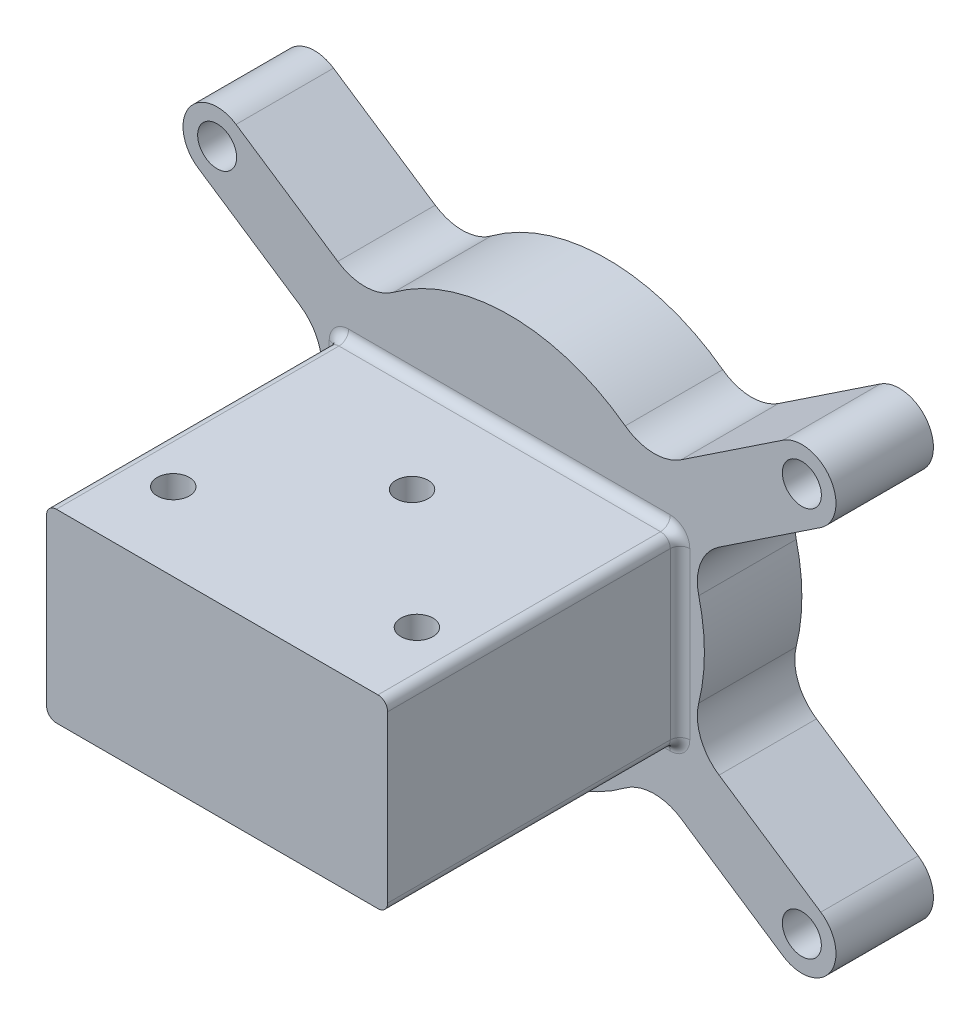
SolidWorks part; units mm, degrees
note: '?' marks a value the reader was unsure of. The reader was unsure of these and kept them because the rebuilt part matched: thickness of "Base-Flange1", "Sheet-Metal8", "Sheet-Metal9", "Sheet-Metal11", "Sheet-Metal12", "Sheet-Metal13".
material "3.3547 (EN-AW 5083)"
ref_plane "Front Plane" through (0, 0, 0) normal (0, 0, 1) x (1, 0, 0)
ref_plane "Top Plane" through (0, 0, 0) normal (0, 1, 0) x (1, 0, 0)
ref_plane "Right Plane" through (0, 0, 0) normal (1, 0, 0) x (0, 0, -1)
ref_axis "Axis1" through (0, 0, -55.9602) along (0, 0, 1)?
sketch "Sketch1" plane through (0, 0, 0) normal (0, 0, 1) x (1, 0, 0)
  line L0 (0, 0) -> (30, 20) construction
  line L2 (14.4428, 13.835) -> (28.0585, 22.9122)
  line L4 (18.3257, 8.0106) -> (31.9415, 17.0878)
  line L5 (0, -44.7868) -> (0, 44.7868) construction
  line L6 (14.4428, -13.835) -> (28.0585, -22.9122)
  line L7 (55, 0) -> (-55, 0) construction
  line L8 (18.3257, -8.0106) -> (31.9415, -17.0878)
  line L9 (-14.4428, -13.835) -> (-28.0585, -22.9122)
  line L10 (-14.4428, 13.835) -> (-28.0585, 22.9122)
  line L11 (-18.3257, 8.0106) -> (-31.9415, 17.0878)
  line L12 (-18.3257, -8.0106) -> (-31.9415, -17.0878)
  line L13 (0, 0) -> (30, -20) construction
  line L14 (0, 0) -> (-30, 20) construction
  line L15 (-30, 20) -> (0, 0) construction
  line L16 (0, 0) -> (-30, -20) construction
  arc A0 (31.9415, 17.0878) -> (28.0585, 22.9122) centre (30, 20) ccw
  arc A1 (28.0585, -22.9122) -> (31.9415, -17.0878) centre (30, -20) ccw
  arc A5 (-31.9415, 17.0878) -> (-28.0585, 22.9122) centre (-30, 20) cw
  arc A6 (-28.0585, -22.9122) -> (-31.9415, -17.0878) centre (-30, -20) cw
  arc A7 (-18.3257, 8.0106) -> (-18.3257, -8.0106) centre (0, 0) ccw
  arc A8 (-14.4428, -13.835) -> (14.4428, -13.835) centre (0, 0) ccw
  arc A9 (14.4428, 13.835) -> (-14.4428, 13.835) centre (0, 0) ccw
  arc A10 (18.3257, -8.0106) -> (18.3257, 8.0106) centre (0, 0) ccw
  point P2 (0, 0)
  dimension "D1" = 7
  dimension "D3" = 40
  dimension "D5" = 40
  dimension "D4" = 20
  dimension "D2" = 30
base flange "Base-Flange1" sketch "Sketch1" thickness 10 reverse thickness direction no parameters "D1"=1.6
sketch "Sketch8" plane through (0, 0, 0) normal (0, 0, 1) x (1, 0, 0)
  arc A0 (31.9415, 17.0878) -> (28.0585, 22.9122) centre (30, 20) ccw construction
  arc A1 (28.0585, -22.9122) -> (31.9415, -17.0878) centre (30, -20) ccw construction
  arc A2 (-31.9415, -17.0878) -> (-28.0585, -22.9122) centre (-30, -20) ccw construction
  arc A3 (-28.0585, 22.9122) -> (-31.9415, 17.0878) centre (-30, 20) ccw construction
  point P0 (-30, 20)
  point P2 (30, -20)
  point P4 (-30, -20)
  point P6 (-30, 20)
  point P11 (30, 20)
hole_wizard "Ø4.0mm Dowel Hole1" positions "Sketch8" profile "Sketch9" hole size "Ø4.0" standard "ISO"
sketch "Sketch9" plane through (-30, 20, 0) normal (1, 0, 0) x (0, -1, 0)
  line L0 (0, 0) -> (0, 17.2017)
  line L1 (0, 17.2017) -> (2, 16)
  line L2 (2, 16) -> (2, 0)
  line L5 (2, 0) -> (0, 0)
  line L10 (0, 17.2017) -> (-2, 16) construction
  line L11 (0, -6.35) -> (0, 107.95) construction
  dimension "Hole Dia." = 4
  dimension "Hole Depth" = 16
  dimension "Drill Angle" = 118
fillet "Fillet1" radius 5 8 edges at (-18.3257, 8.0106, -5) (-18.3257, -8.0106, -5) (-14.4428, -13.835, -5) (14.4428, -13.835, -5) (18.3257, -8.0106, -5) (18.3257, 8.0106, -5) (14.4428, 13.835, -5) (-14.4428, 13.835, -5)
sketch "Sketch10" plane through (0, 0, 0) normal (0, 0, 1) x (1, 0, 0)
  line L2 (-7, -7.1414) -> (-7, 7.1414)
  line L4 (7, -7.1414) -> (7, 7.1414)
  line L5 (-7, -7.1414) -> (7, 7.1414) construction
  line L6 (-7, 7.1414) -> (7, -7.1414) construction
  arc A0 (-7, -7.1414) -> (7, -7.1414) centre (0, 0) ccw
  arc A1 (7, 7.1414) -> (-7, 7.1414) centre (0, 0) ccw
  dimension "D1" = 20
  dimension "D2" = 14
sketch "Sketch15" plane through (0, 0, -10) normal (0, 0, -1) x (-1, 0, 0)
  point P0 (0, 0)
hole_wizard "Ø4.0mm Dowel Hole2" positions "Sketch15" profile "Sketch16" hole size "Ø4.0" standard "ISO"
sketch "Sketch16" plane through (0, 0, -10) normal (1, 0, 0) x (0, 1, 0)
  line L0 (0, 0) -> (0, 17.2017)
  line L1 (0, 17.2017) -> (2, 16)
  line L2 (2, 16) -> (2, 0)
  line L5 (2, 0) -> (0, 0)
  line L10 (0, 17.2017) -> (-2, 16) construction
  line L11 (0, -6.35) -> (0, 107.95) construction
  dimension "Hole Dia." = 4
  dimension "Hole Depth" = 16
  dimension "Drill Angle" = 118
sketch "Sketch17" plane through (0, 0, 0) normal (0, 0, 1) x (1, 0, 0)
  line L1 (-17.5, -9.5) -> (17.5, -9.5)
  line L2 (-17.5, -9.5) -> (-17.5, 9.5)
  line L3 (-17.5, 9.5) -> (17.5, 9.5)
  line L4 (17.5, -9.5) -> (17.5, 9.5)
  line L5 (-17.5, -9.5) -> (17.5, 9.5) construction
  line L6 (-17.5, 9.5) -> (17.5, -9.5) construction
  point P0 (0, 0)
  dimension "D1" = 19
  dimension "D2" = 35
extrude "Boss-Extrude1" add sketch "Sketch17" along normal blind 30
sketch "Sketch18" plane through (0, 9.5, 0) normal (0, 1, 0) x (1, 0, 0)
  line L0 (0, -44.7868) -> (0, 44.7868) construction
  line L1 (-17.5, -30) -> (-17.5, 0) construction
  line L2 (17.5, -30) -> (17.5, 0) construction
  line L3 (-44.2539, 0) -> (44.2539, 0) construction
  circle A0 centre (0, -10) radius 1.65
  circle A1 centre (-12.5, -22) radius 1.65
  circle A2 centre (12.5, -22) radius 1.65
  dimension "D1" = 3.3
  dimension "D2" = 5
  dimension "D3" = 5
  dimension "D4" = 10
  dimension "D5" = 22
extrude "Cut-Extrude1" cut sketch "Sketch18" against normal through all normal cut yes
fillet "Fillet2" radius 1 8 edges at (17.5, 0, 0) (0, 9.5, 0) (0, -9.5, 0) (-17.5, 0, 0) (-17.5, -9.5, 15) (17.5, -9.5, 15) (17.5, 9.5, 15) (-17.5, 9.5, 15)
sketch "Bend-Lines1" [suppressed] plane through (0, 0, 0) normal (0, 1, 0) x (1, 0, 0)
sketch "Bounding-Box1" [suppressed] plane through (0, 0, 0) normal (0, 1, 0) x (1, 0, 0)
sheet metal parameters "Sheet-Metal8" thickness 10 parameters "D1"=1.6, "D7"=3
flat pattern "Flat-Pattern8" [suppressed]
sketch "Bend-Lines2" plane through (0, 0, 0) normal (0, 1, 0) x (1, 0, 0)
sketch3d "Bounding-Box2" [suppressed]
  line L0 (-63.4997, 3.4999, 0) -> (3.4998, 3.4998, 0) construction
  line L1 (-63.4998, -43.4997, 0) -> (3.4997, -43.4998, 0) construction
  line L2 (-63.4997, 3.4999, 0) -> (-63.4998, -43.4997, 0) construction
  line L3 (3.4998, 3.4998, 0) -> (3.4997, -43.4998, 0) construction
sheet metal parameters "Sheet-Metal9" thickness 10 parameters "D1"=1.6, "D7"=3
flat pattern "Flat-Pattern8"
sketch "Bend-Lines2" plane through (0, 0, 0) normal (0, 1, 0) x (1, 0, 0)
sketch3d "Bounding-Box2" [suppressed]
  line L0 (-63.4997, 3.4999, 0) -> (3.4998, 3.4998, 0) construction
  line L1 (-63.4998, -43.4997, 0) -> (3.4997, -43.4998, 0) construction
  line L2 (-63.4997, 3.4999, 0) -> (-63.4998, -43.4997, 0) construction
  line L3 (3.4998, 3.4998, 0) -> (3.4997, -43.4998, 0) construction
sheet metal parameters "Sheet-Metal11" thickness 10 parameters "D1"=1.6, "D7"=3
flat pattern "Flat-Pattern8"
sketch "Bend-Lines2" plane through (0, 0, 0) normal (0, 1, 0) x (1, 0, 0)
sketch3d "Bounding-Box2" [suppressed]
  line L0 (-63.4997, 3.4999, 0) -> (3.4998, 3.4998, 0) construction
  line L1 (-63.4998, -43.4997, 0) -> (3.4997, -43.4998, 0) construction
  line L2 (-63.4997, 3.4999, 0) -> (-63.4998, -43.4997, 0) construction
  line L3 (3.4998, 3.4998, 0) -> (3.4997, -43.4998, 0) construction
sheet metal parameters "Sheet-Metal12" thickness 10 parameters "D1"=1.6, "D7"=3
flat pattern "Flat-Pattern8"
sketch "Bend-Lines2" plane through (0, 0, 0) normal (0, 1, 0) x (1, 0, 0)
sketch3d "Bounding-Box2" [suppressed]
  line L0 (-63.4997, 3.4999, 0) -> (3.4998, 3.4998, 0) construction
  line L1 (-63.4998, -43.4997, 0) -> (3.4997, -43.4998, 0) construction
  line L2 (-63.4997, 3.4999, 0) -> (-63.4998, -43.4997, 0) construction
  line L3 (3.4998, 3.4998, 0) -> (3.4997, -43.4998, 0) construction
sheet metal parameters "Sheet-Metal13" thickness 10 parameters "D1"=1.6, "D7"=3
flat pattern "Flat-Pattern8"
sketch "Bend-Lines2" plane through (0, 0, 0) normal (0, 1, 0) x (1, 0, 0)
sketch3d "Bounding-Box2" [suppressed]
  line L0 (-63.4997, 3.4999, 0) -> (3.4998, 3.4998, 0) construction
  line L1 (-63.4998, -43.4997, 0) -> (3.4997, -43.4998, 0) construction
  line L2 (-63.4997, 3.4999, 0) -> (-63.4998, -43.4997, 0) construction
  line L3 (3.4998, 3.4998, 0) -> (3.4997, -43.4998, 0) construction
